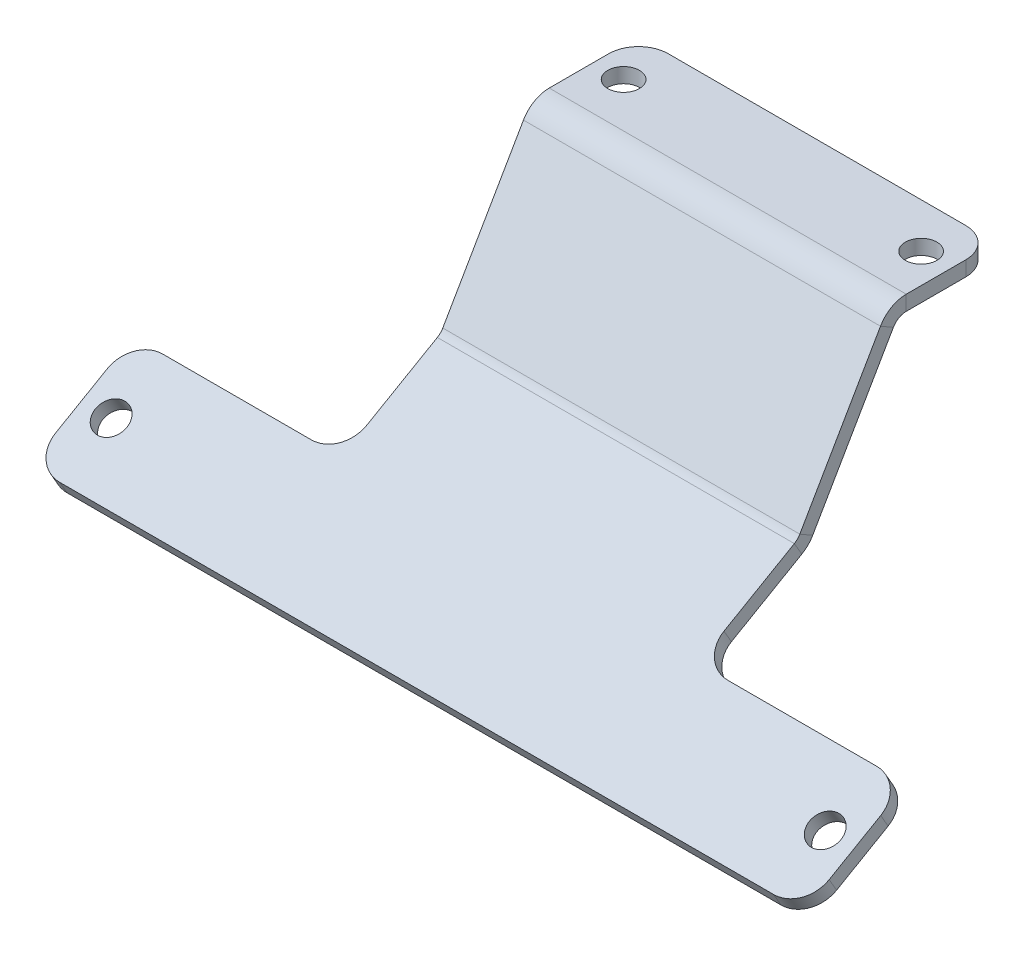
SolidWorks part; units mm, degrees
note: The reader was unsure of these and kept them because the rebuilt part matched: flange length of "Edge-Flange1", "Edge-Flange2".
ref_plane "Front Plane" through (0, 0, 0) normal (0, 0, 1) x (1, 0, 0)
ref_plane "Top Plane" through (0, 0, 0) normal (0, 1, 0) x (1, 0, 0)
ref_plane "Right Plane" through (0, 0, 0) normal (1, 0, 0) x (0, 0, -1)
sketch "Sketch1" plane through (0, 0, 0) normal (0, 1, 0) x (1, 0, 0)
  line L0 (-31.75, -9.525) -> (31.75, -9.525) construction
  line L1 (-38.1, 0) -> (38.1, 0)
  line L2 (-38.1, 0) -> (-38.1, -19.05)
  line L3 (-38.1, -19.05) -> (38.1, -19.05)
  line L4 (38.1, 0) -> (38.1, -19.05)
  point P7 (0, -9.525)
  dimension "D1" = 76.2
  dimension "D2" = 19.05
  dimension "D3" = 63.5
  dimension "D4" = 9.525
base flange "Base-Flange1" sketch "Sketch1" thickness 3.175 reverse thickness direction no parameters "D1"=3.175
edge flange "Edge-Flange1" sketch "Sketch8" flange angle 120 flange length 38.1 flange position bend outside bend radius 3.175 thickness 3.175 relief rectangular parameters "D6"=10
sketch "Sketch8" plane through (0, -3.175, 19.05) normal (0, 0.5, 0.866) x (-1, 0, 0)
  line L0 (38.1, 0) -> (-38.1, 0) construction
  line L1 (38.1, 0) -> (-38.1, 0)
  line L2 (-38.1, 0) -> (-38.1, 36.2669)
  line L3 (-38.1, 36.2669) -> (38.1, 36.2669)
  line L4 (38.1, 36.2669) -> (38.1, 0)
bend "EdgeBend1" bend radius 3.175 bend angle 60 parameters "D5"=1
edge flange "Edge-Flange2" sketch "Sketch11" flange angle 150 flange length 50.8 flange position bend outside bend radius 3.175 thickness 3.175 relief rectangular parameters "D6"=10
sketch "Sketch11" plane through (0, -32.9956, 41.7662) normal (0, -0.866, -0.5) x (1, 0, 0)
  line L0 (-38.1, 0) -> (38.1, 0) construction
  line L1 (-38.1, 0) -> (38.1, 0)
  line L2 (-38.1, 0) -> (-38.1, 49.9493)
  line L3 (-38.1, 49.9493) -> (38.1, 49.9493)
  line L4 (38.1, 49.9493) -> (38.1, 0)
bend "EdgeBend2" bend radius 3.175 bend angle 30 parameters "D5"=2
hole_wizard "1/4 Clearance Hole1" positions "Sketch12" profile "Sketch13" hole size "1/4" standard "ANSI Inch" end condition through all
sketch "Sketch12" plane through (0, 0, 0) normal (0, 1, 0) x (1, 0, 0)
  point P0 (-31.75, -9.525)
  point P3 (31.75, -9.525)
sketch "Sketch13" plane through (-31.75, 0, 9.525) normal (1, 0, 0) x (0, 0, 1)
  line L0 (0, 0) -> (0, 61.4566)
  line L1 (0, 61.4566) -> (3.3782, 61.4566)
  line L2 (3.3782, 61.4566) -> (3.3782, 0)
  line L5 (3.3782, 0) -> (0, 0)
  line L11 (0, -6.35) -> (0, 107.95) construction
  dimension "Thru Hole Dia." = 6.7564
  dimension "Thru Hole Depth" = 61.4566
sketch "Sketch17" plane through (0, -7.0298, -4.0586) normal (0, 0.866, 0.5) x (1, 0, 0)
  line L3 (38.1, -103.3544) -> (-38.1, -103.3544) construction
  line L4 (-82.55, -77.9544) -> (82.55, -77.9544)
  line L5 (-82.55, -77.9544) -> (-82.55, -103.3544)
  line L6 (-82.55, -103.3544) -> (82.55, -103.3544)
  line L7 (82.55, -77.9544) -> (82.55, -103.3544)
  point P0 (50.4296, -68.005)
  point P1 (0, -103.3544)
  point P2 (0, -103.3544)
  point P13 (0, 0)
  point P14 (0, 0)
  dimension "D1" = 165.1
  dimension "D2" = 25.4
extrude "Boss-Extrude1" add sketch "Sketch17" against normal up to surface (3.175 mm away) up to face at (0, -49.182, 62.6011)
hole_wizard "1/4 Clearance Hole3" positions "Sketch15" profile "Sketch16" hole size "1/4" standard "ANSI Inch" end condition through all
sketch "Sketch15" plane through (0, -7.0298, -4.0586) normal (0, 0.866, 0.5) x (1, 0, 0)
  line L0 (-82.55, -90.6544) -> (82.55, -90.6544) construction
  line L3 (82.55, -103.3544) -> (82.55, -77.9544) construction
  line L4 (-82.55, -77.9544) -> (-82.55, -103.3544) construction
  point P9 (-76.2, -90.6544)
  point P11 (76.2, -90.6544)
  point P14 (0, -90.6544)
  dimension "D1" = 152.4
  dimension "D2" = 76.2
sketch "Sketch16" plane through (76.2, -52.357, 74.4504) normal (1, 0, 0) x (0, -0.5, 0.866)
  line L0 (0, 0) -> (0, 45.1057)
  line L1 (0, 45.1057) -> (3.3782, 45.1057)
  line L2 (3.3782, 45.1057) -> (3.3782, 0)
  line L5 (3.3782, 0) -> (0, 0)
  line L11 (0, -6.35) -> (0, 107.95) construction
  dimension "Thru Hole Dia." = 6.7564
  dimension "Thru Hole Depth" = 45.1057
fillet "Fillet1" radius 6.35 8 edges at (-82.55, -47.3818, 62.6581) (-82.55, -60.0818, 84.6551) (82.55, -60.0818, 84.6551) (82.55, -47.3818, 62.6581) (-38.1, -1.5875, 0) (38.1, -1.5875, 0) (-38.1, -47.3818, 62.6581) (38.1, -47.3818, 62.6581)
sketch "Bend-Lines1" [suppressed] plane through (0, 0, 0) normal (0, 1, 0) x (1, 0, 0)
sketch "Bounding-Box1" [suppressed] plane through (0, 0, 0) normal (0, 1, 0) x (1, 0, 0)
sheet metal parameters "Sheet-Metal1" thickness 3.175 parameters "D1"=3.175
flat pattern "Flat-Pattern1" [suppressed]
sketch "Bend-Lines2" plane through (0, 0, 0) normal (0, 1, 0) x (1, 0, 0)
sketch3d "Bounding-Box2" [suppressed]
  line L0 (-38.1, -19.05, 0) -> (38.1, -19.05, 0) construction
  line L1 (-38.1, 0, 0) -> (38.1, 0, 0) construction
  line L2 (-38.1, -19.05, 0) -> (-38.1, 0, 0) construction
  line L3 (38.1, -19.05, 0) -> (38.1, 0, 0) construction
sheet metal parameters "Sheet-Metal2" thickness 3.175 parameters "D1"=3.175
flat pattern "Flat-Pattern1"
sketch "Bend-Lines2" plane through (0, 0, 0) normal (0, 1, 0) x (1, 0, 0)
  line L0 (-38.1, -15.1382) -> (38.1, -15.1382) construction
  line L1 (-38.1, -15.1382) -> (38.1, -15.1382) construction
sketch3d "Bounding-Box2" [suppressed]
  line L0 (38.1, -51.1596, 0) -> (-38.1, -51.1596, 0) construction
  line L1 (38.1, 0, 0) -> (-38.1, 0, 0) construction
  line L2 (38.1, -51.1596, 0) -> (38.1, 0, 0) construction
  line L3 (-38.1, -51.1596, 0) -> (-38.1, 0, 0) construction
bend of the flat pattern "Flatten-<EdgeBend1>1"
sheet metal parameters "Sheet-Metal3" thickness 3.175 parameters "D1"=3.175
flat pattern "Flat-Pattern1"
sketch "Bend-Lines2" plane through (0, 0, 0) normal (0, 1, 0) x (1, 0, 0)
  line L0 (-38.1, -20.6375) -> (38.1, -20.6375) construction
  line L1 (-38.1, -20.6375) -> (38.1, -20.6375) construction
  line L2 (-38.1, -58.2463) -> (38.1, -58.2463) construction
  line L3 (-38.1, -58.2463) -> (38.1, -58.2463) construction
sketch3d "Bounding-Box2" [suppressed]
  line L0 (-38.1, 0, 0) -> (-38.1, -77.1823, 0) construction
  line L1 (38.1, 0, 0) -> (38.1, -77.1823, 0) construction
  line L2 (-38.1, 0, 0) -> (38.1, 0, 0) construction
  line L3 (-38.1, -77.1823, 0) -> (38.1, -77.1823, 0) construction
bend of the flat pattern "Flatten-<EdgeBend1>1"
bend of the flat pattern "Flatten-<EdgeBend2>1"
sheet metal parameters "Sheet-Metal4" thickness 3.175 parameters "D1"=3.175
flat pattern "Flat-Pattern1"
sketch "Bend-Lines2" plane through (0, 0, 0) normal (0, 1, 0) x (1, 0, 0)
  line L0 (-38.1, -20.6375) -> (38.1, -20.6375) construction
  line L1 (-38.1, -20.6375) -> (38.1, -20.6375) construction
  line L2 (-38.1, -58.2463) -> (38.1, -58.2463) construction
  line L3 (-38.1, -58.2463) -> (38.1, -58.2463) construction
sketch3d "Bounding-Box2" [suppressed]
  line L0 (-38.1, 0, 0) -> (-38.1, -77.1823, 0) construction
  line L1 (38.1, 0, 0) -> (38.1, -77.1823, 0) construction
  line L2 (-38.1, 0, 0) -> (38.1, 0, 0) construction
  line L3 (-38.1, -77.1823, 0) -> (38.1, -77.1823, 0) construction
bend of the flat pattern "Flatten-<EdgeBend1>1"
bend of the flat pattern "Flatten-<EdgeBend2>1"
sheet metal parameters "Sheet-Metal5" thickness 3.175 parameters "D1"=3.175
flat pattern "Flat-Pattern1"
sketch "Bend-Lines2" plane through (0, 0, 0) normal (0, 1, 0) x (1, 0, 0)
  line L0 (-38.1, -20.6375) -> (38.1, -20.6375) construction
  line L1 (-38.1, -20.6375) -> (38.1, -20.6375) construction
  line L2 (-38.1, -58.2463) -> (38.1, -58.2463) construction
  line L3 (-38.1, -58.2463) -> (38.1, -58.2463) construction
sketch3d "Bounding-Box2" [suppressed]
  line L0 (-82.55, -108.9323, 0) -> (82.55, -108.9323, 0) construction
  line L1 (-82.55, 0, 0) -> (82.55, 0, 0) construction
  line L2 (-82.55, -108.9323, 0) -> (-82.55, 0, 0) construction
  line L3 (82.55, -108.9323, 0) -> (82.55, 0, 0) construction
bend of the flat pattern "Flatten-<EdgeBend1>1"
bend of the flat pattern "Flatten-<EdgeBend2>1"
sheet metal parameters "Sheet-Metal6" thickness 3.175 parameters "D1"=3.175
flat pattern "Flat-Pattern1"
sketch "Bend-Lines2" plane through (0, 0, 0) normal (0, 1, 0) x (1, 0, 0)
  line L0 (-38.1, -20.6375) -> (38.1, -20.6375) construction
  line L1 (-38.1, -20.6375) -> (38.1, -20.6375) construction
  line L2 (-38.1, -58.2463) -> (38.1, -58.2463) construction
  line L3 (-38.1, -58.2463) -> (38.1, -58.2463) construction
sketch3d "Bounding-Box2" [suppressed]
  line L0 (76.2, -77.1823, 0) -> (-76.2, -77.1823, 0) construction
  line L1 (76.2, 0, 0) -> (-76.2, 0, 0) construction
  line L2 (76.2, -77.1823, 0) -> (76.2, 0, 0) construction
  line L3 (-76.2, -77.1823, 0) -> (-76.2, 0, 0) construction
bend of the flat pattern "Flatten-<EdgeBend1>1"
bend of the flat pattern "Flatten-<EdgeBend2>1"
equation "\"D2@Sketch15\"=\"D1@Sketch15\"/2"
